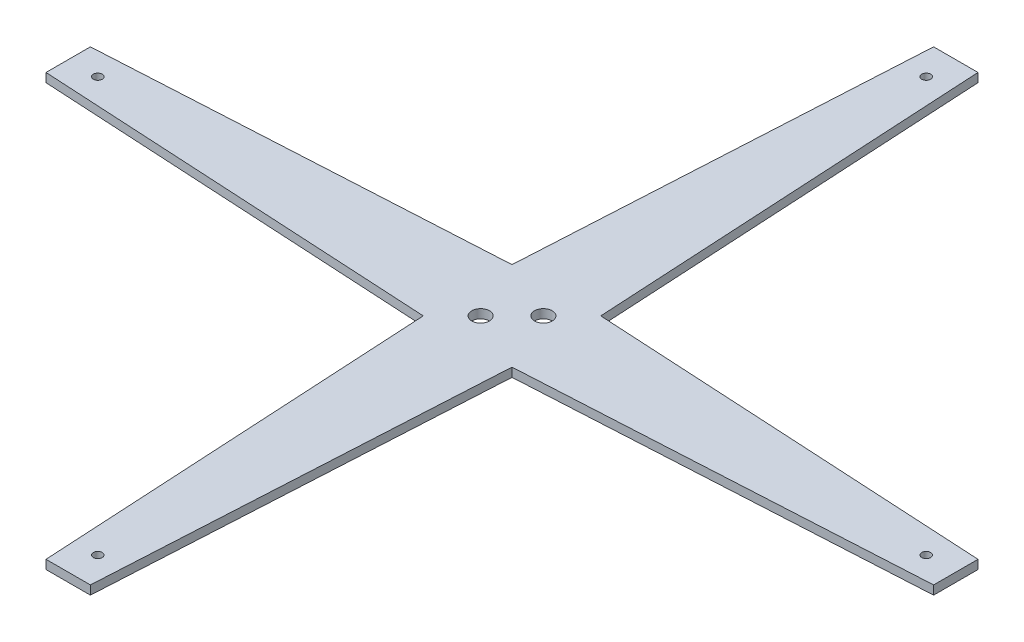
SolidWorks part; units mm, degrees
ref_plane "Front Plane" through (0, 0, 0) normal (0, 0, 1) x (1, 0, 0)
ref_plane "Top Plane" through (0, 0, 0) normal (0, 1, 0) x (1, 0, 0)
ref_plane "Right Plane" through (0, 0, 0) normal (1, 0, 0) x (0, 0, -1)
sketch "Sketch1" plane through (0, 0, 0) normal (0, 1, 0) x (1, 0, 0)
  line L0 (-15, 15) -> (-150, 7.5)
  line L1 (-150, 7.5) -> (-150, -7.5)
  line L2 (-150, -7.5) -> (-15, -15)
  line L3 (0, 0) -> (-50000, 0) construction
  line L4 (0, 0) -> (0, -50000) construction
  line L5 (15, 15) -> (7.5, 150)
  line L6 (7.5, 150) -> (-7.5, 150)
  line L7 (-7.5, 150) -> (-15, 15)
  line L8 (15, -15) -> (150, -7.5)
  line L9 (150, -7.5) -> (150, 7.5)
  line L10 (150, 7.5) -> (15, 15)
  line L11 (-15, -15) -> (-7.5, -150)
  line L12 (-7.5, -150) -> (7.5, -150)
  line L13 (7.5, -150) -> (15, -15)
  line L14 (-15, -15) -> (15, 15) construction
  circle A0 centre (0, 140) radius 1.5
  circle A1 centre (140, 0) radius 1.5
  circle A2 centre (0, -140) radius 1.5
  circle A3 centre (-140, 0) radius 1.5
  circle A4 centre (-5.3033, -5.3033) radius 3
  circle A5 centre (5.3033, 5.3033) radius 3
  point P24 (0, 0)
  point P29 (0, 0)
  dimension "D9" = 3
  dimension "D13" = 6
  dimension "D14" = 6
  dimension "D1" = 15
  dimension "D2" = 15
  dimension "D3" = 7.5
  dimension "D4" = 7.5
  dimension "D5" = 150
  dimension "D6" = 15
  dimension "D7" = 15
  dimension "D10" = 10
  dimension "D11" = 4
  dimension "D12" = 10
  dimension "D15" = 15
  dimension "D16" = 7.5
  dimension "D8" = 4
extrude "Boss-Extrude1" add sketch "Sketch1" along normal blind 3
